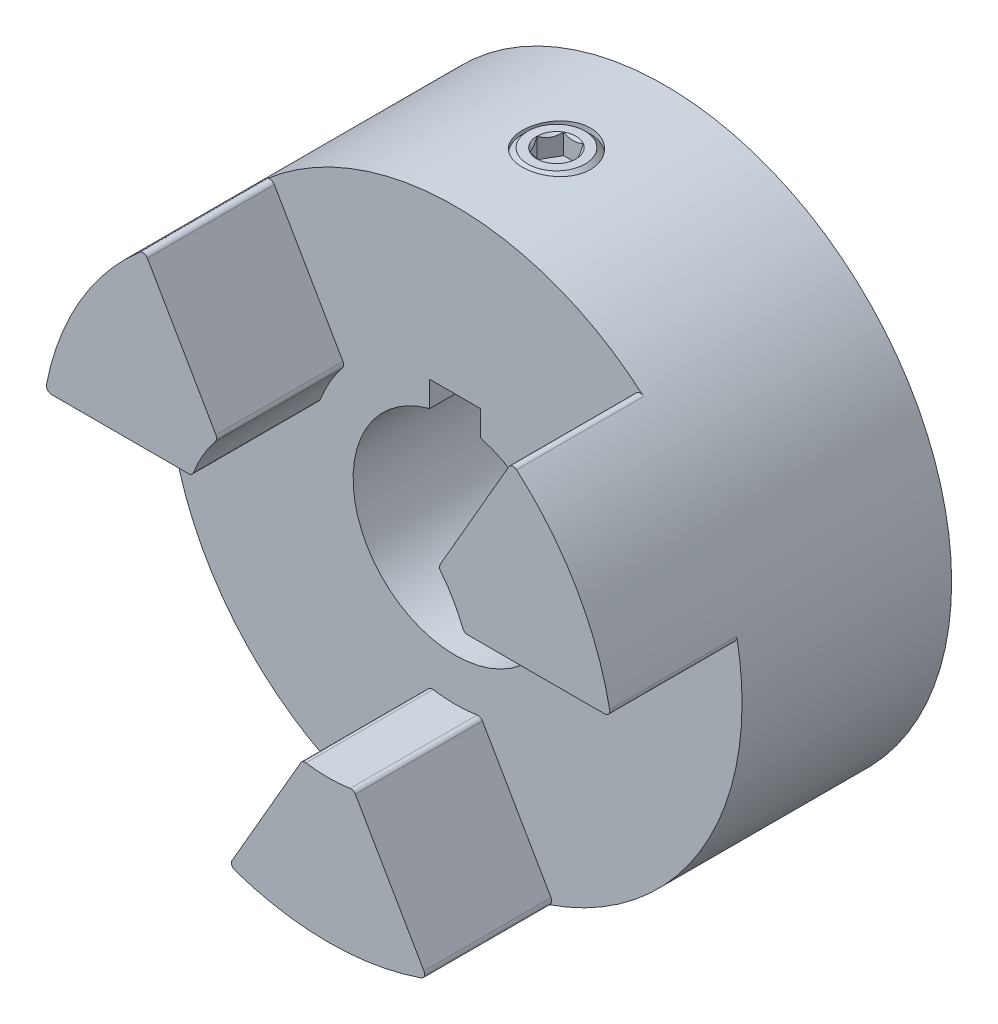
SolidWorks part; units mm, degrees
ref_plane "Front" through (0, 0, 0) normal (0, 0, 1) x (1, 0, 0)
ref_plane "Top" through (0, 0, 0) normal (0, 1, 0) x (1, 0, 0)
ref_plane "Right" through (0, 0, 0) normal (1, 0, 0) x (0, 0, -1)
sketch "Sketch3" plane through (0, 0, 0) normal (1, 0, 0) x (0, 0, -1)
  line L0 (27.3844, 0) -> (-27.3844, 0) construction
  circle A0 centre (0, 0) radius 5.1149 construction
  circle A1 centre (0, 0) radius 9.525 construction
  circle A2 centre (0, 0) radius 26.7891 construction
  point P7 (0, 5.1149)
  point P8 (0, -5.1149)
  point P9 (0, 9.525)
  point P10 (0, -9.525)
  point P11 (0, 26.7891)
  point P12 (0, -26.7891)
  point P13 (6.7469, 0)
  point P14 (-5.1149, 0)
  point P15 (5.1149, 0)
  point P16 (-5.1149, 26.7891)
  point P17 (27.3844, 26.7891)
  point P18 (6.7469, 26.7891)
  dimension "OD" = 53.5781
  dimension "Shaft Dia" = 19.05
  dimension "Overall Lg" = 54.7687
  dimension "Bore Depth" = 20.6375
  dimension "Lug Lg" = 11.8618
sketch "Sketch1" plane through (0, 0, 0) normal (0, 0, 1) x (1, 0, 0)
  circle A0 centre (0, 0) radius 26.7891
  circle A1 centre (0, 0) radius 9.525 construction
extrude "Boss-Extrude1" add sketch "Sketch1" against normal up to vertex (27.3844 mm away) from vertex up to point (0, 0, -27.3844) starting at point (0, 0, -6.7469)
sketch "Sketch10" [suppressed] plane through (0, 0, -3.5719) normal (0, 0, 1) x (1, 0, 0)
  arc A14 (-1.0963, -4.1108) -> (1.0963, -4.1108) centre (0, 0) ccw
  arc A15 (-3.4409, -7.1529) -> (-1.0963, -4.1108) centre (-9.5758, 0) ccw
  arc A19 (1.0963, -4.1108) -> (3.4409, -7.1529) centre (9.5758, 0) ccw
  circle A32 centre (0, 0) radius 7.9375 construction
  arc A33 (-3.4409, -7.1529) -> (3.4409, -7.1529) centre (0, 0) ccw
  point P0 (0, -4.2545)
  point P1 (0, -7.9375)
  dimension "D1" = 3.683
  dimension "D4" = 9.4234
  dimension "D2" = 6.8819
  dimension "D3" = 2.1926
extrude "Boss-Extrude4" [suppressed] add sketch "Sketch10" along normal up to vertex up to point (0, 0, 5.1149)
fillet "Fillet2" [suppressed] radius 0.381
other "Move Face3" [suppressed] parameters "D1"=90
pattern_circular "CirPattern2" [suppressed] count 2 over 360 of bodies 116
sketch "Sketch11" [suppressed] plane through (0, 0, -5.9531) normal (0, 0, 1) x (1, 0, 0)
  arc A0 (-1.5825, -7.8835) -> (1.5738, -7.8835) centre (-0.0044, -0.0397) ccw
  arc A1 (-1.5825, -7.8835) -> (-2.9616, -8.354) centre (-1.8681, -9.3029) ccw
  arc A2 (-2.9616, -8.354) -> (-4.9794, -11.8231) centre (5.1535, -15.3956) ccw
  arc A3 (-4.9794, -11.8231) -> (-4.4308, -12.9555) centre (-4.1442, -12.1175) ccw
  arc A4 (-4.4308, -12.9555) -> (4.4176, -12.96) centre (0, 0) ccw
  arc A5 (4.4176, -12.96) -> (4.9692, -11.8231) centre (4.1308, -12.1185) ccw
  arc A6 (4.9692, -11.8231) -> (2.9523, -8.354) centre (-5.1643, -15.3938) ccw
  arc A7 (2.9523, -8.354) -> (1.5738, -7.8835) centre (1.8592, -9.3021) ccw
  circle A8 centre (0, 0) radius 13.6922 construction
  point P18 (-0.007, -13.6922)
  point P19 (-0.0044, -8.0407)
  dimension "D1" = 1.4478
  dimension "D2" = 8.001
  dimension "D3" = 10.7442
  dimension "D4" = 0.889
  dimension "D9" = 5.6515
  dimension "D5" = 5.072
  dimension "D6" = 3.1563
  dimension "D7" = 5.9139
  dimension "D8" = 9.9486
extrude "Boss-Extrude5" [suppressed] add sketch "Sketch11" along normal up to vertex up to point (0, 0, 5.1149)
other "Move Face1" [suppressed] parameters "D1"=90
pattern_circular "CirPattern3" [suppressed] count 2 over 360 of bodies 118
sketch "Sketch12" [suppressed] plane through (0, 0, -6.1516) normal (0, 0, 1) x (1, 0, 0)
  line L0 (-5.1097, -10.267) -> (-8.533, -13.6894)
  line L1 (8.533, -13.6894) -> (5.1097, -10.267)
  arc A0 (-2.3442, -9.4968) -> (2.3442, -9.4968) centre (0, 0) ccw
  arc A1 (-2.3442, -9.4968) -> (-5.1097, -10.267) centre (-3.0443, -12.333) ccw
  arc A2 (-8.533, -13.6894) -> (-8.3299, -15.1215) centre (-7.8934, -14.3292) ccw
  arc A3 (-8.3299, -15.1215) -> (8.3299, -15.1215) centre (0, 0) ccw
  arc A4 (8.3299, -15.1215) -> (8.533, -13.6894) centre (7.8934, -14.3292) ccw
  arc A5 (5.1097, -10.267) -> (2.3442, -9.4968) centre (3.0443, -12.333) ccw
  circle A6 centre (0, 0) radius 17.2641 construction
  point P16 (0, -9.7819)
  point P17 (0, -17.2641)
  dimension "D1" = 7.4822
  dimension "D2" = 10.2193
  dimension "D3" = 4.6884
  dimension "D4" = 17.066
  dimension "D5" = 16.6598
extrude "Boss-Extrude6" [suppressed] add sketch "Sketch12" along normal up to vertex up to point (0, 0, 5.1149)
other "Move Face2" [suppressed] parameters "D1"=90
pattern_circular "CirPattern4" [suppressed] count 2 over 360 of bodies 120
sketch "Sketch2" plane through (0, 0, -6.7469) normal (0, 0, 1) x (1, 0, 0)
  line L0 (-9.2385, -25.1456) -> (-2.385, -13.2749)
  line L2 (2.385, -13.2749) -> (9.2385, -25.1456)
  circle A0 centre (0, 0) radius 26.7891 construction
  arc A1 (-9.2385, -25.1456) -> (9.2385, -25.1456) centre (0, 0) ccw
  arc A2 (-2.385, -13.2749) -> (2.385, -13.2749) centre (0, 0) ccw
  circle A3 centre (0, 0) radius 4.572 construction
  dimension "Spider Inner body Dia" = 26.9748
  dimension "Spider Leg Thickness" = 9.144
  dimension "D4" = 4.7699
  dimension "D1" = 60
extrude "Boss-Extrude2" add sketch "Sketch2" along normal up to vertex (11.8618 mm away) up to point (0, 0, 5.1149)
fillet "Fillet1" radius 0.477 4 edges at (2.385, -13.2749, -0.816) (-2.385, -13.2749, -0.816)
pattern_circular "CirPattern1" count 3 over 360 about axis through (0, 0, -27.3844) along (0, 0, 1) of "Boss-Extrude2", "Fillet1"
sketch "Sketch15" plane through (0, 0, 0) normal (0, 0, 1) x (1, 0, 0)
  circle A0 centre (0, 0) radius 9.525
extrude "Cut-Extrude5" cut sketch "Sketch15" against normal through all and the other way through all
chamfer "Chamfer1" distance 1.0716 angle 56 2 edges at (26.7891, 0, -27.3844) (9.525, 0, -27.3844) first distance on face at (26.7891, 0, -27.3844) first distance on face at (9.525, 0, -6.7469)
sketch "Sketch4" plane through (0, 0, 0) normal (0, 0, 1) x (1, 0, 0)
  line L1 (-2.3813, 11.6038) -> (2.3812, 11.6038)
  line L2 (-2.3813, 11.6038) -> (-2.3813, 9.2225)
  line L4 (2.3812, 11.6038) -> (2.3813, 9.2225)
  arc A1 (2.3813, 9.2225) -> (-2.3813, 9.2225) centre (0, 0) ccw
  circle A2 centre (0, 0) radius 9.525 construction
  dimension "Keyway Ht" = 2.3813
  dimension "Keyway Wd" = 4.7625
extrude "Cut-Extrude1" cut sketch "Sketch4" against normal through all and the other way through all
sketch "Sketch5" plane through (0, 0, 0) normal (0, 1, 0) x (1, 0, 0)
  line L1 (0, -46.4939) -> (0, 46.4939) construction
  circle A0 centre (0, 16.2084) radius 3.175
  dimension "Screw Dia" = 6.35
  dimension "Screw Offset" = 11.176
extrude "Cut-Extrude2" cut sketch "Sketch5" along normal through all
ref_plane "Plane1" through (0, 26.7891, 0) normal (0, 1, 0) x (-1, 0, 0)
sketch "Sketch6" plane through (0, 26.7891, 0) normal (0, 1, 0) x (-1, 0, 0)
  circle A1 centre (0, -16.2084) radius 3.175
  circle A2 centre (0, -16.2084) radius 3.175
  dimension "D1" = 0
extrude "Boss-Extrude3" add sketch "Sketch6" against normal blind 7.9375 separate body
sketch "Sketch8" plane through (0, 26.7891, 0) normal (0, 1, 0) x (1, 0, 0)
  line L1 (0.9165, 14.6209) -> (1.8331, 16.2084)
  line L2 (1.8331, 16.2084) -> (0.9165, 17.7959)
  line L3 (0.9165, 17.7959) -> (-0.9165, 17.7959)
  line L4 (-0.9165, 17.7959) -> (-1.8331, 16.2084)
  line L5 (-1.8331, 16.2084) -> (-0.9165, 14.6209)
  line L6 (-0.9165, 14.6209) -> (0.9165, 14.6209)
  circle A0 centre (0, 16.2084) radius 1.5875 construction
  dimension "D1" = 3.175
extrude "Cut-Extrude3" cut sketch "Sketch8" against normal blind 1.905
sketch "Sketch9" plane through (0, 26.7891, 0) normal (0, 1, 0) x (1, 0, 0)
  circle A0 centre (0, 16.2084) radius 1.8331
extrude "Cut-Extrude4" cut sketch "Sketch9" against normal through all draft 45
chamfer "Chamfer3" distance 0.508 angle 45 1 edges at (0, 26.7891, -13.0334)
chamfer "Chamfer4" distance 1.0795 angle 45 1 edges at (0, 18.8516, -13.0334)
sketch "Sketch16" [suppressed] plane through (0, 0, -61.9125) normal (0, 0, -1) x (-1, 0, 0)
  circle A0 centre (0, 0) radius 50.8
  dimension "D1" = 101.6
extrude "Cut-Extrude6" [suppressed] cut sketch "Sketch16" against normal blind 30.3022 flip side to cut
chamfer "Chamfer5" [suppressed] distance 1.778 angle 56
fillet "Fillet3" [suppressed] radius 1.27
move or copy body "Body-Move/Copy1" [suppressed] bodies to move or copy 115 copy no translate (0, -6.35, 0)
sketch "Sketch17" [suppressed] plane through (0, 0, -67.8656) normal (0, 0, -1) x (-1, 0, 0)
  circle A0 centre (0, 0) radius 53.975
  dimension "D1" = 107.95
extrude "Cut-Extrude7" [suppressed] cut sketch "Sketch17" against normal blind 36.576 flip side to cut
move or copy body "Body-Move/Copy2" [suppressed] bodies to move or copy 115 copy no translate (0, -9.525, 0)
fillet "Fillet4" [suppressed] radius 2.54
fillet "Fillet5" [suppressed] radius 1.27
equation "\"D1@Chamfer1\" = \"OD@Sketch3\" * .02"
equation "\"D1@Fillet1\" = \"D4@Sketch2\" * .1"
equation "\"D1@Sketch8\" = \"Screw Dia@Sketch5\" * .5"
equation "\"D1@Cut-Extrude3\" = \"Screw Dia@Sketch5\" * .3"
equation "\"D1@Chamfer3\" = \"Screw Dia@Sketch5\" * .08"
equation "\"D1@Chamfer4\" = \"Screw Dia@Sketch5\" * .17"
